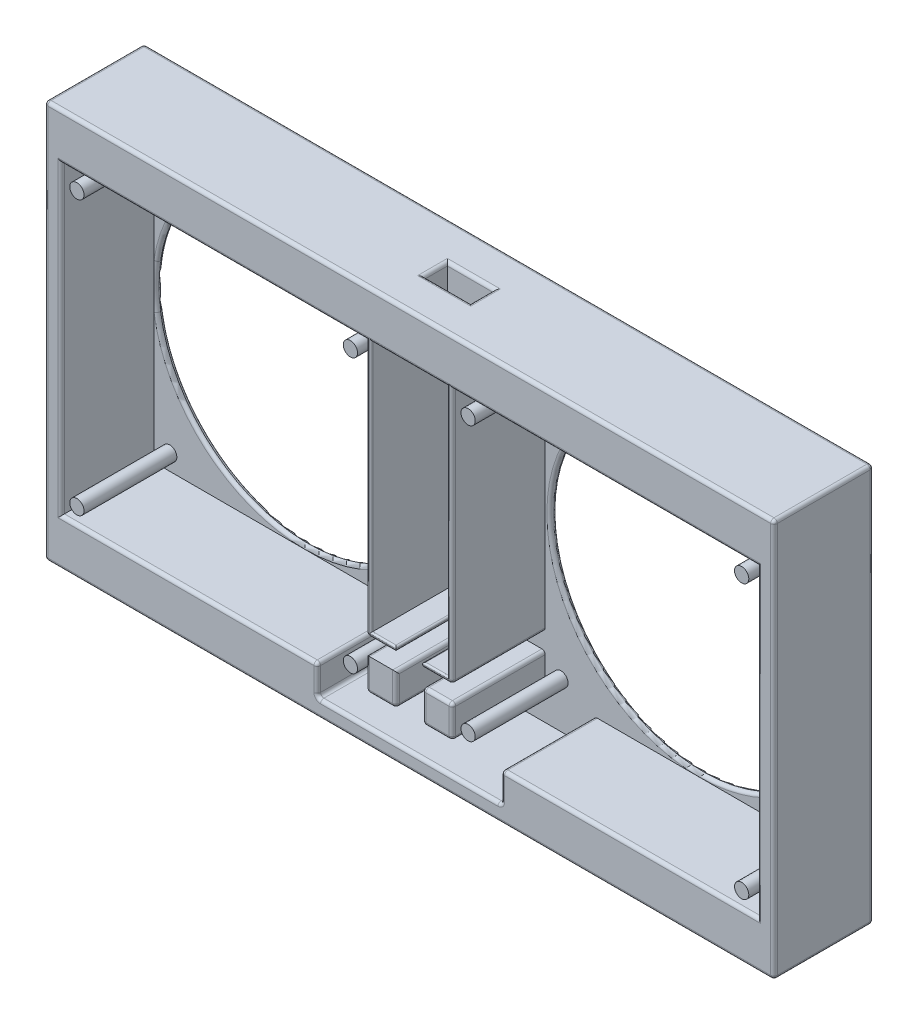
SolidWorks part; units mm, degrees
ref_plane "前视基准面" through (0, 0, 0) normal (0, 0, 1) x (1, 0, 0)
ref_plane "上视基准面" through (0, 0, 0) normal (0, 1, 0) x (1, 0, 0)
ref_plane "右视基准面" through (0, 0, 0) normal (1, 0, 0) x (0, 0, -1)
other "Configuration Table"
sketch "草图1" plane through (0, 0, 0) normal (0, 0, 1) x (1, 0, 0)
  line L1 (-110, -60) -> (110, -60)
  line L2 (-110, -60) -> (-110, 60)
  line L3 (-110, 60) -> (110, 60)
  line L4 (110, -60) -> (110, 60)
  line L5 (-110, -60) -> (110, 60) construction
  line L6 (-110, 60) -> (110, -60) construction
  point P0 (0, 0)
  dimension "D1" = 220
  dimension "D2" = 120
extrude "凸台-拉伸1" add sketch "草图1" along normal blind 30 contours L2 L1 L4 L3
sketch "草图2" plane through (0, 0, 30) normal (0, 0, 1) x (1, 0, 0)
  line L0 (-110, 0) -> (0, 0) construction
  line L1 (0, 0) -> (110, 0) construction
  line L2 (110, -60) -> (110, 60) construction
  line L3 (-110, -60) -> (-110, 60) construction
  line L4 (-110, 60) -> (110, 60) construction
  line L5 (-105, -46) -> (-27.75, -46)
  line L6 (-105, -46) -> (-105, 46)
  line L7 (-105, 46) -> (-13, 46)
  line L8 (-13, -46) -> (-13, -36.25)
  line L9 (-105, -46) -> (-13, 46) construction
  line L10 (-105, 46) -> (-13, -46) construction
  line L11 (-27.75, -46) -> (-27.75, -55)
  line L12 (-17.75, -41.25) -> (-100.25, -41.25) construction
  line L13 (-17.75, -41.25) -> (-17.75, 41.25) construction
  line L14 (-17.75, 41.25) -> (-100.25, 41.25) construction
  line L15 (-100.25, -41.25) -> (-100.25, 41.25) construction
  line L16 (-17.75, -41.25) -> (-100.25, 41.25) construction
  line L17 (-17.75, 41.25) -> (-100.25, -41.25) construction
  line L18 (-27.75, -55) -> (-22.75, -55)
  line L19 (-22.75, -55) -> (-22.75, -46)
  line L20 (-22.75, -46) -> (-13, -46)
  line L21 (-13, -36.25) -> (-4, -36.25)
  line L22 (-4, -36.25) -> (-4, -31.25)
  line L23 (-4, -31.25) -> (-13, -31.25)
  line L24 (-13, -31.25) -> (-13, 46)
  circle A0 centre (-100.25, 41.25) radius 2.15
  circle A1 centre (-17.75, 41.25) radius 2.15
  circle A2 centre (-17.75, -41.25) radius 2.15
  circle A3 centre (-100.25, -41.25) radius 2.15
  point P8 (-59, 0)
  point P12 (-59, 0)
  dimension "D6" = 4.3
  dimension "D7" = 4.3
  dimension "D8" = 4.3
  dimension "D9" = 4.3
  dimension "D1" = 92
  dimension "D2" = 14
  dimension "D3" = 5
  dimension "D4" = 82.5
  dimension "D5" = 82.5
  dimension "D10" = 9
  dimension "D11" = 5
  dimension "D12" = 5
  dimension "D13" = 5
  dimension "D14" = 5
  dimension "D15" = 9
extrude "切除-拉伸1" cut sketch "草图2" against normal blind 28
ref_plane "基准面1" through (0, 0, 12) normal (0, 0, 1) x (1, 0, 0)
sketch "草图3" plane through (0, 0, 12) normal (0, 0, 1) x (1, 0, 0)
  line L0 (0, 0) -> (-109.8399, 0) construction
  line L1 (-13, -46) -> (-13, -36.25) construction
  circle A0 centre (-59.5, 0) radius 45
  point P5 (0, 0)
  dimension "D1" = 90
  dimension "D2" = 46.5
extrude "切除-拉伸2" cut sketch "草图3" against normal through all
ref_plane "基准面2" through (0, 0, 0) normal (1, 0, 0) x (0, 0, -1)
mirror "镜向1" about plane through (0, 0, 0) normal (1, 0, 0) of "切除-拉伸2", "切除-拉伸1"
sketch "草图5" plane through (0, 0, 30) normal (0, 0, 1) x (1, 0, 0)
  line L0 (-4, -29.75) -> (-4, -31.25)
  line L1 (-11.5, 46) -> (11.5, 46)
  line L2 (-11.5, 46) -> (-11.5, -29.75)
  line L3 (-11.5, -29.75) -> (-4, -29.75)
  line L4 (11.5, 46) -> (11.5, -29.75)
  line L5 (-4, -31.25) -> (-4, -36.25)
  line L6 (-4, -36.25) -> (-4, -46)
  line L7 (-4, -46) -> (-13, -46)
  line L8 (-13, 46) -> (-105, 46) construction
  line L9 (-13, -31.25) -> (-13, 46) construction
  line L10 (13, -31.25) -> (13, 46) construction
  line L11 (-4, -31.25) -> (-13, -31.25) construction
  line L12 (-13, -46) -> (-22.75, -46)
  line L13 (-22.75, -46) -> (-22.75, -55)
  line L14 (-22.75, -55) -> (22.75, -55)
  line L15 (22.75, -55) -> (22.75, -46)
  line L16 (22.75, -46) -> (13, -46)
  line L17 (4, -46) -> (4, -36.25)
  line L18 (4, -36.25) -> (4, -31.25)
  line L19 (4, -31.25) -> (4, -29.75)
  line L20 (13, -46) -> (4, -46)
  line L21 (4, -29.75) -> (11.5, -29.75)
  dimension "D1" = 1.5
  dimension "D2" = 1.5
  dimension "D3" = 1.5
extrude "切除-拉伸3" cut sketch "草图5" against normal blind 28
sketch "草图6" plane through (0, 46, 0) normal (0, -1, 0) x (1, 0, 0)
  line L0 (0, 30) -> (0, 0) construction
  line L1 (-110, 30) -> (110, 30) construction
  line L2 (-110, 15) -> (110, 15) construction
  line L3 (-110, 30) -> (-110, 0) construction
  line L4 (110, 30) -> (110, 0) construction
  line L6 (-7, 11.5) -> (7, 11.5)
  line L7 (-7, 11.5) -> (-7, 18.5)
  line L8 (-7, 18.5) -> (7, 18.5)
  line L9 (7, 11.5) -> (7, 18.5)
  line L10 (-7, 11.5) -> (7, 18.5) construction
  line L11 (-7, 18.5) -> (7, 11.5) construction
  point P11 (0, 15)
  dimension "D1" = 7
  dimension "D2" = 14
extrude "切除-拉伸4" cut sketch "草图6" against normal through all
sketch "草图7" plane through (0, 0, 2) normal (0, 0, 1) x (1, 0, 0)
  line L0 (0, 46) -> (0, -60) construction
  line L1 (11.5, 46) -> (-11.5, 46) construction
  line L2 (-110, -60) -> (110, -60) construction
  line L3 (11.5, 46) -> (-11.5, 46) construction
  circle A0 centre (0, 44) radius 1
  dimension "D1" = 2
  dimension "D2" = 2
extrude "切除-拉伸5" cut sketch "草图7" against normal through all
pattern_linear "阵列(线性)2" count 25 spacing 3 along (0, -1, 0) of "切除-拉伸5"
pattern_linear "阵列(线性)3" count 4 spacing 3 along (1, 0, 0) of "阵列(线性)2", "切除-拉伸5"
pattern_linear "阵列(线性)4" count 4 spacing 3 along (-1, 0, 0) of "阵列(线性)2", "切除-拉伸5"
fillet "圆角1" radius 1 58 edges at (14.5, 0, 2) (14.5, 0, 0) (-4, -46, 16) (0, -60, 30) (4, -46, 16) (-8.5, -46, 30) (8.5, -46, 30) (0, 46, 30) (-110, 0, 30) (7, 60, 15) (0, 60, 11.5) (-7, 60, 15) (0, 60, 18.5) (7, 46, 15) (0, 46, 18.5) (-7, 46, 15) (0, 46, 11.5) (-13, -31.25, 16) (-4, -31.25, 16) (-4, -36.25, 16) (-13, -36.25, 16) (-13, -46, 16) (-27.75, -55, 16) (-27.75, -46, 16) (-13, 7.375, 30) (-59, 46, 30) (-105, 0, 30) (-66.375, -46, 30) (-27.75, -50.5, 30) (0, -55, 30) (-13, -41.125, 30) (-8.5, -31.25, 30) (0, 60, 30) (-110, 0, 0) (0, -60, 0) (110, 0, 0) (0, 60, 0) (-14.5, 0, 0) (-104.5, 0, 2) (-110, 60, 15) (-110, -60, 15) (110, -60, 15) (13, 7.375, 30) (110, 60, 15) (13, -31.25, 16) (59, 46, 30) (105, 0, 30) (66.375, -46, 30) (27.75, -50.5, 30) (27.75, -46, 16) (27.75, -55, 16) (13, -41.125, 30) (13, -46, 16) (13, -36.25, 16) (4, -36.25, 16) (8.5, -31.25, 30) (4, -31.25, 16) (110, 0, 30)
fillet "圆角2" radius 0.5 6 edges at (-4, -29.75, 16) (-7.75, -29.75, 30) (4, -29.75, 16) (7.75, -29.75, 30) (11.5, 8.625, 30) (-11.5, 8.625, 30)
